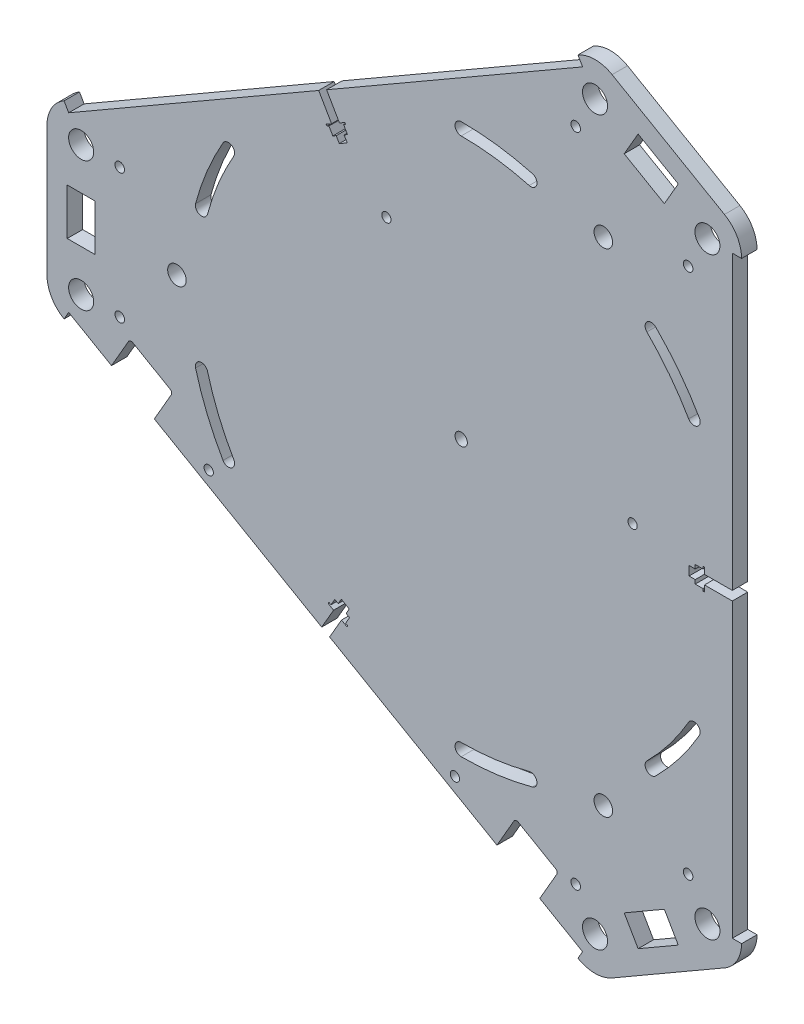
SolidWorks part; units mm, degrees
material "6061-T6 Black anodised"
ref_plane "Front Plane" through (0, 0, 0) normal (0, 0, 1) x (1, 0, 0)
ref_plane "Top Plane" through (0, 0, 0) normal (0, 1, 0) x (1, 0, 0)
ref_plane "Right Plane" through (0, 0, 0) normal (1, 0, 0) x (0, 0, -1)
sketch "Sketch1" plane through (0, 0, 0) normal (0, 0, 1) x (1, 0, 0)
  line L0 (0, 0) -> (-123, 0) construction
  line L1 (-123, 21) -> (-123, -21) construction
  line L2 (-131.05, 20.9815) -> (-131.05, -21) construction
  line L3 (0, 0) -> (61.5, 106.5211) construction
  line L4 (0, 0) -> (61.5, -106.5211) construction
  line L5 (43.3135, 117.0211) -> (79.6865, 96.0211) construction
  line L6 (79.6865, -96.0211) -> (43.3135, -117.0211) construction
  line L7 (47.3385, 123.9926) -> (83.7115, 102.9926) construction
  line L8 (83.7115, -102.9926) -> (47.3385, -123.9926) construction
  line L9 (-127.025, 27.9715) -> (39.2885, 123.9926)
  line L10 (87.7365, 96.0211) -> (87.7365, -96.0211)
  line L11 (39.2885, -123.9926) -> (-127.025, -27.9715)
  line L12 (70.2452, 106.6682) -> (65.7452, 98.874)
  line L13 (-127.5, -7.5) -> (-118.5, -7.5)
  line L14 (-127.5, -7.5) -> (-127.5, 7.5)
  line L15 (-127.5, 7.5) -> (-118.5, 7.5)
  line L16 (-118.5, -7.5) -> (-118.5, 7.5)
  line L17 (-127.5, -7.5) -> (-118.5, 7.5) construction
  line L18 (-127.5, 7.5) -> (-118.5, -7.5) construction
  line L19 (52.7548, 106.374) -> (65.7452, 98.874)
  line L20 (57.2548, 114.1682) -> (52.7548, 106.374)
  line L21 (57.2548, 114.1682) -> (70.2452, 106.6682)
  line L22 (57.2548, -114.1682) -> (52.7548, -106.374)
  line L23 (65.7452, -98.874) -> (52.7548, -106.374)
  line L24 (70.2452, -106.6682) -> (65.7452, -98.874)
  line L25 (70.2452, -106.6682) -> (57.2548, -114.1682)
  line L26 (-110.5, 21) -> (-110.5, -21) construction
  line L27 (36.342, 121.0461) -> (12.4205, 79.6129) construction
  line L28 (12.4205, 79.6129) -> (-75.157, 29.05) construction
  line L29 (-75.157, 29.05) -> (-123, 29.05) construction
  line L30 (-75.157, -29.05) -> (-123, -29.05) construction
  line L31 (-75.157, -29.05) -> (12.4205, -79.6129) construction
  line L32 (12.4205, -79.6129) -> (36.342, -121.0461) construction
  line L33 (85.158, -89.398) -> (62.7365, -50.5629) construction
  line L34 (62.7365, -50.5629) -> (62.7365, 50.5629) construction
  line L35 (62.7365, 50.5629) -> (85.158, 89.398) construction
  line L36 (12.4205, 79.6129) -> (62.7365, 50.5629) construction
  line L37 (62.7365, -50.5629) -> (12.4205, -79.6129) construction
  line L38 (-75.157, -29.05) -> (-75.157, 29.05) construction
  line L39 (-127.025, -27.9715) -> (-128.525, -30.5696)
  line L40 (-134.05, -21) -> (-134.05, 21)
  line L41 (-127.025, 27.9715) -> (-128.525, 30.5696)
  line L42 (39.2885, -123.9926) -> (37.7885, -126.5907)
  line L43 (87.7365, 96.0211) -> (90.7365, 96.0211)
  line L44 (39.2885, 123.9926) -> (37.7885, 126.5907)
  line L45 (48.8415, -126.5889) -> (85.6951, -105.2947)
  line L46 (87.7365, -96.0211) -> (90.7365, -96.0211)
  line L47 (48.8385, 126.5907) -> (85.2115, 105.5907)
  line L49 (-93.5, 2.5981) -> (-95, 0) construction
  line L50 (-95, 0) -> (-93.5, -2.5981) construction
  line L51 (-93.5, -2.5981) -> (-90.5, -2.5981) construction
  line L52 (-90.5, -2.5981) -> (-89, 0) construction
  line L53 (-89, 0) -> (-90.5, 2.5981) construction
  line L54 (-90.5, 2.5981) -> (-93.5, 2.5981) construction
  circle A0 centre (-123, 21) radius 4.05
  circle A1 centre (-123, -21) radius 4.05
  arc A2 (-127.025, 27.9715) -> (-131.05, 20.9815) centre (-123, 21) ccw construction
  arc A3 (-131.05, -21) -> (-127.025, -27.9715) centre (-123, -21) ccw construction
  circle A4 centre (43.3135, 117.0211) radius 4.05
  circle A5 centre (79.6865, 96.0211) radius 4.05
  circle A6 centre (79.6865, -96.0211) radius 4.05
  circle A7 centre (43.3135, -117.0211) radius 4.05
  arc A8 (39.2885, -123.9926) -> (47.3385, -123.9926) centre (43.3135, -117.0211) ccw construction
  arc A9 (83.7115, -102.9926) -> (87.7365, -96.0211) centre (79.6865, -96.0211) ccw construction
  arc A10 (87.7365, 96.0211) -> (83.7115, 102.9926) centre (79.6865, 96.0211) ccw construction
  arc A11 (47.3385, 123.9926) -> (39.2885, 123.9926) centre (43.3135, 117.0211) ccw construction
  circle A12 centre (-110.5, 21) radius 1.55
  circle A13 centre (-110.5, -21) radius 1.55
  circle A14 centre (73.4365, 85.1958) radius 1.55
  circle A15 centre (37.0635, 106.1958) radius 1.55
  circle A16 centre (37.0635, -106.1958) radius 1.55
  circle A17 centre (73.4365, -85.1958) radius 1.55
  circle A18 centre (0, 0) radius 62.7365 construction
  circle A19 centre (0, 0) radius 2
  circle A20 centre (8.2272, 4.75) radius 2 construction
  circle A21 centre (8.2272, -4.75) radius 2 construction
  circle A22 centre (0, -9.5) radius 2 construction
  circle A23 centre (0, 9.5) radius 2 construction
  circle A24 centre (-8.2272, -4.75) radius 2 construction
  circle A25 centre (-8.2272, 4.75) radius 2 construction
  arc A26 (-134.05, -21) -> (-128.525, -30.5696) centre (-123, -21) ccw
  arc A27 (-134.05, 21) -> (-128.525, 30.5696) centre (-123, 21) cw
  arc A28 (37.7885, -126.5907) -> (48.8415, -126.5889) centre (43.3135, -117.0211) ccw
  arc A29 (85.6951, -105.2947) -> (90.7365, -96.0211) centre (79.6865, -96.0211) ccw
  arc A30 (90.7365, 96.0211) -> (85.2115, 105.5907) centre (79.6865, 96.0211) ccw
  arc A31 (48.8385, 126.5907) -> (37.7885, 126.5907) centre (43.3135, 117.0211) ccw
  circle A32 centre (-92, 0) radius 3
  circle A33 centre (46, 79.6743) radius 3
  circle A34 centre (46, -79.6743) radius 3
  point P43 (0, 0)
  point P44 (-110.5, 0)
  point P57 (0, 0)
  point P84 (0, 0)
  point P86 (0, 0)
  point P111 (0, 0)
  dimension "D3" = 8.1
  dimension "D5" = 4
  dimension "D10" = 3.1
  dimension "D13" = 25
  dimension "D14" = 4
  dimension "D15" = 9.5
  dimension "D17" = 3
  dimension "D18" = 6
  dimension "D1" = 123
  dimension "D2" = 42
  dimension "D4" = 120
  dimension "D6" = 9
  dimension "D7" = 15
  dimension "D9" = 42
  dimension "D11" = 12.5
  dimension "D19" = 92
  dimension "D8" = 3
  dimension "D12" = 3
  dimension "D16" = 6
  dimension "D20" = 3
extrude "Boss-Extrude1" add sketch "Sketch1" along normal blind 5
sketch "Sketch2" plane through (0, 0, 5) normal (0, 0, 1) x (1, 0, 0)
  line L0 (0, 0) -> (-43.8683, -75.9821) construction
  line L1 (-127.025, -27.9715) -> (39.2885, -123.9926) construction
  line L2 (0, 0) -> (-43.8683, 75.9821) construction
  line L3 (39.2885, 123.9926) -> (-127.025, 27.9715) construction
  line L4 (0, 0) -> (87.7365, 0) construction
  line L5 (87.7365, -96.0211) -> (87.7365, 96.0211) construction
  line L6 (87.7365, 1.48) -> (78.7365, 1.48)
  line L7 (78.7365, 1.48) -> (78.7365, 3.5)
  line L8 (78.7365, 3.5) -> (78.2365, 3.5)
  line L9 (78.2365, 3.5) -> (78.2365, 2.75)
  line L10 (78.2365, 2.75) -> (75.7365, 2.75)
  line L11 (75.7365, 2.75) -> (75.7365, 1.48)
  line L12 (75.7365, 1.48) -> (73.7365, 1.48)
  line L13 (73.7365, 1.48) -> (73.7365, -1.48)
  line L14 (87.7365, -1.48) -> (78.7365, -1.48)
  line L15 (78.7365, -1.48) -> (78.7365, -3.5)
  line L16 (78.7365, -3.5) -> (78.2365, -3.5)
  line L17 (78.2365, -3.5) -> (78.2365, -2.75)
  line L18 (78.2365, -2.75) -> (75.7365, -2.75)
  line L19 (75.7365, -2.75) -> (75.7365, -1.48)
  line L20 (75.7365, -1.48) -> (73.7365, -1.48)
  line L21 (87.7365, -1.48) -> (87.7365, 1.48)
  line L22 (-43.2361, -77.8471) -> (-38.7361, -70.0528)
  line L23 (-38.7361, -70.0528) -> (-36.9867, -71.0628)
  line L24 (-36.9867, -71.0628) -> (-36.7367, -70.6298)
  line L25 (-36.7367, -70.6298) -> (-37.3862, -70.2548)
  line L26 (-37.3862, -70.2548) -> (-36.1362, -68.0898)
  line L27 (-36.1362, -68.0898) -> (-37.2361, -67.4548)
  line L28 (-37.2361, -67.4548) -> (-36.2361, -65.7227)
  line L29 (-36.2361, -65.7227) -> (-38.7995, -64.2427)
  line L30 (-45.7995, -76.3671) -> (-41.2995, -68.5728)
  line L31 (-41.2995, -68.5728) -> (-43.0489, -67.5628)
  line L32 (-43.0489, -67.5628) -> (-42.7989, -67.1298)
  line L33 (-42.7989, -67.1298) -> (-42.1494, -67.5048)
  line L34 (-42.1494, -67.5048) -> (-40.8994, -65.3398)
  line L35 (-40.8994, -65.3398) -> (-39.7995, -65.9748)
  line L36 (-39.7995, -65.9748) -> (-38.7995, -64.2427)
  line L37 (-45.7995, -76.3671) -> (-43.2361, -77.8471)
  line L38 (-46.449, 75.2421) -> (-41.949, 67.4478)
  line L39 (-41.949, 67.4478) -> (-43.6984, 66.4378)
  line L40 (-43.6984, 66.4378) -> (-43.4484, 66.0048)
  line L41 (-43.4484, 66.0048) -> (-42.7989, 66.3798)
  line L42 (-42.7989, 66.3798) -> (-41.5489, 64.2148)
  line L43 (-41.5489, 64.2148) -> (-40.449, 64.8498)
  line L44 (-40.449, 64.8498) -> (-39.449, 63.1177)
  line L45 (-39.449, 63.1177) -> (-36.8856, 64.5977)
  line L46 (-43.8856, 76.7221) -> (-39.3856, 68.9278)
  line L47 (-39.3856, 68.9278) -> (-37.6362, 69.9378)
  line L48 (-37.6362, 69.9378) -> (-37.3862, 69.5048)
  line L49 (-37.3862, 69.5048) -> (-38.0357, 69.1298)
  line L50 (-38.0357, 69.1298) -> (-36.7857, 66.9648)
  line L51 (-36.7857, 66.9648) -> (-37.8856, 66.3298)
  line L52 (-37.8856, 66.3298) -> (-36.8856, 64.5977)
  line L53 (-43.8856, 76.7221) -> (-46.449, 75.2421)
  point P28 (73.7365, 0)
  point P47 (-37.5178, -64.9827)
  point P62 (0.0125, 0.0072)
  point P64 (0, 0)
  point P65 (0.0125, 0.0072)
  point P67 (-38.1673, 63.8577)
  point P68 (-0.6495, -0.375)
  dimension "D1" = 0.5
  dimension "D2" = 2.5
  dimension "D3" = 2
  dimension "D4" = 14
  dimension "D5" = 2.96
  dimension "D6" = 7
  dimension "D7" = 5.5
  dimension "D8" = 3
extrude "Cut-Extrude1" cut sketch "Sketch2" against normal through all
sketch "Sketch3" plane through (0, 0, 5) normal (0, 0, 1) x (1, 0, 0)
  line L0 (-112.8026, -37.3375) -> (-100.6782, -44.3375)
  line L1 (-113.1686, -35.9715) -> (-107.6686, -26.4452)
  line L2 (-99.3122, -43.9715) -> (-93.8122, -34.4452)
  line L3 (-106.3026, -26.0792) -> (-94.1782, -33.0792)
  line L4 (-127.025, -27.9715) -> (-45.15, -75.2421) construction
  line L5 (-128.525, -30.5696) -> (-127.025, -27.9715) construction
  line L6 (-24.2054, 50.075) -> (-81.7054, -49.5179) construction
  line L7 (-24.2054, 50.075) -> (55.4689, 4.075) construction
  line L8 (-81.7054, -49.5179) -> (-2.0311, -95.518) construction
  line L9 (55.4689, 4.075) -> (-2.0311, -95.518) construction
  line L10 (-24.2054, 50.075) -> (-2.0311, -95.518) construction
  line L11 (-81.7054, -49.5179) -> (55.4689, 4.075) construction
  line L12 (25.4321, -115.9926) -> (30.9321, -106.4663)
  line L13 (-127.025, -27.9715) -> (-45.15, -75.2421) construction
  line L14 (-37.5178, -64.9827) -> (0, 0) construction
  line L15 (24.066, -116.3586) -> (11.9417, -109.3586)
  line L16 (11.5757, -107.9926) -> (17.0757, -98.4663)
  line L17 (30.566, -105.1003) -> (18.4417, -98.1003)
  line L18 (-36.2361, -65.7227) -> (-38.7995, -64.2427) construction
  arc A0 (-113.1686, -35.9715) -> (-112.8026, -37.3375) centre (-112.3026, -36.4715) ccw
  arc A1 (-100.6782, -44.3375) -> (-99.3122, -43.9715) centre (-100.1782, -43.4715) ccw
  arc A2 (-93.8122, -34.4452) -> (-94.1782, -33.0792) centre (-94.6782, -33.9452) ccw
  arc A3 (-106.3026, -26.0792) -> (-107.6686, -26.4452) centre (-106.8026, -26.9452) ccw
  circle A4 centre (-81.7054, -49.5179) radius 1.5
  circle A5 centre (-2.0311, -95.518) radius 1.5
  circle A6 centre (55.4689, 4.075) radius 1.5
  circle A7 centre (-24.2054, 50.075) radius 1.5
  arc A8 (30.566, -105.1003) -> (30.9321, -106.4663) centre (30.066, -105.9663) cw
  arc A9 (25.4321, -115.9926) -> (24.066, -116.3586) centre (24.566, -115.4926) cw
  arc A10 (11.9417, -109.3586) -> (11.5757, -107.9926) centre (12.4417, -108.4926) cw
  arc A11 (17.0757, -98.4663) -> (18.4417, -98.1003) centre (17.9417, -98.9663) cw
  point P17 (-13.1183, -22.7215)
  dimension "D3" = 1
  dimension "D8" = 3
  dimension "D1" = 16
  dimension "D2" = 16
  dimension "D4" = 12
  dimension "D5" = 4
  dimension "D6" = 92
  dimension "D7" = 115
extrude "Cut-Extrude2" cut sketch "Sketch3" against normal through all
sketch "Sketch4" plane through (0, 0, 5) normal (0, 0, 1) x (1, 0, 0)
  line L0 (-72, 14.5) -> (-72, -14.5) construction
  line L1 (48.5574, 55.1038) -> (23.4426, 69.6038) construction
  line L2 (23.4426, -69.6038) -> (48.5574, -55.1038) construction
  circle A0 centre (-72, 14.5) radius 1.375
  circle A1 centre (-72, -14.5) radius 1.375
  circle A2 centre (48.5574, 55.1038) radius 1.375
  circle A3 centre (23.4426, 69.6038) radius 1.375
  circle A4 centre (36, 62.3538) radius 4 construction
  circle A5 centre (23.4426, -69.6038) radius 1.375
  circle A6 centre (-72, 0) radius 4 construction
  circle A7 centre (48.5574, -55.1038) radius 1.375
  circle A8 centre (36, -62.3538) radius 4 construction
  point P21 (0, 0)
  point P24 (0, 0)
  dimension "D1" = 29
  dimension "D2" = 8
  dimension "D3" = 2.75
  dimension "D4" = 72
  dimension "D5" = 3
extrude "Cut-Extrude3" [suppressed] cut sketch "Sketch4" against normal through all
sketch "Sketch5" plane through (0, 0, 5) normal (0, 0, 1) x (1, 0, 0)
  line L0 (-104, 0) -> (0, 0) construction
  line L1 (0, 0) -> (52, 90.0666) construction
  line L2 (0, 0) -> (52, -90.0666) construction
  line L3 (-104, 0) -> (52, 90.0666) construction
  line L4 (52, 90.0666) -> (52, -90.0666) construction
  line L5 (52, -90.0666) -> (-104, 0) construction
  line L6 (87.7365, 1.48) -> (87.7365, 96.0211) construction
  circle A0 centre (-123, 21) radius 4.05 construction
  circle A1 centre (0, 0) radius 23 construction
  circle A2 centre (0, 0) radius 87.7365 construction
  point P0 (-104, 0)
  point P9 (11.5, 19.9186)
  point P10 (11.5, -19.9186)
  point P11 (-23, 0)
  dimension "D1" = 19
  dimension "D5" = 46
  dimension "D7" = 175.4731
  dimension "D2" = 120
  dimension "D3" = 120
  dimension "D4" = 180.1333
  dimension "D6" = 81
ref_axis "Axis1" through (0, 0, 5) along (0, 0, -1)
sketch "Sketch6" plane through (0, 0, 5) normal (0, 0, 1) x (1, 0, 0)
  line L0 (-73.6122, 42.5) -> (-77.0763, 44.5) construction
  line L1 (-92, 0) -> (0, 0) construction
  line L3 (-82.1037, 21.9996) -> (-85.9674, 23.0349) construction
  arc A0 (-77.0763, 44.5) -> (-85.9674, 23.0349) centre (0, 0) ccw
  arc A2 (-73.6122, 42.5) -> (-82.1037, 21.9996) centre (0, 0) ccw
  arc A3 (-73.6122, 42.5) -> (-77.0763, 44.5) centre (-75.3442, 43.5) ccw
  arc A4 (-85.9674, 23.0349) -> (-82.1037, 21.9996) centre (-84.0355, 22.5173) ccw
  arc A5 (-73.6122, -42.5) -> (-77.0763, -44.5) centre (-75.3442, -43.5) cw
  arc A6 (-77.0763, -44.5) -> (-85.9674, -23.0349) centre (0, 0) cw
  arc A7 (-85.9674, -23.0349) -> (-82.1037, -21.9996) centre (-84.0355, -22.5173) cw
  arc A8 (-73.6122, -42.5) -> (-82.1037, -21.9996) centre (0, 0) cw
  circle A9 centre (-92, 0) radius 3 construction
  dimension "D1" = 15
  dimension "D3" = 4
  dimension "D2" = 30
extrude "Cut-Extrude4" cut sketch "Sketch6" against normal through all
pattern_circular "CirPattern1" count 3 over 360 about axis through (0, 0, 5) along (0, 0, -1) of "Cut-Extrude4"
